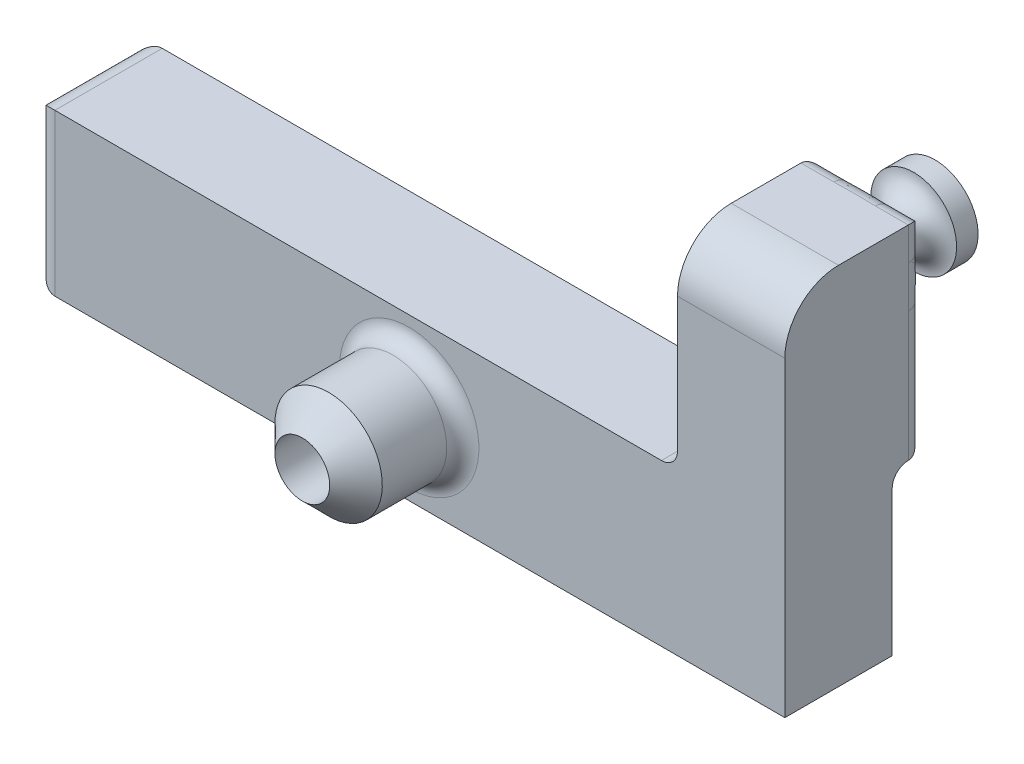
SolidWorks part; units mm, degrees
ref_plane "Front Plane" through (0, 0, 0) normal (0, 0, 1) x (1, 0, 0)
ref_plane "Top Plane" through (0, 0, 0) normal (0, 1, 0) x (1, 0, 0)
ref_plane "Right Plane" through (0, 0, 0) normal (1, 0, 0) x (0, 0, -1)
sketch "Sketch1" plane through (0, 0, 0) normal (0, 0, 1) x (1, 0, 0)
  line L0 (-35, -7.5) -> (35, -7.5)
  line L1 (-35, -7.5) -> (-35, 7.5)
  line L2 (35, -7.5) -> (35, 7.5)
  line L3 (-35, 7.5) -> (35, 7.5)
  line L4 (-35, -7.5) -> (35, 7.5) construction
  line L5 (35, -7.5) -> (-35, 7.5) construction
  circle A0 centre (0, 0) radius 2.55
  point P1 (0, 0)
  dimension "D3" = 5.1
  dimension "D1" = 70
  dimension "D2" = 15
  dimension "D4" = 35
extrude "Boss-Extrude1" add sketch "Sketch1" along normal blind 10
sketch "Sketch5" plane through (0, 0, 0) normal (0, 0, -1) x (-1, 0, 0)
  line L0 (-35, 26.5) -> (-25, 26.5)
  line L1 (-35, 26.5) -> (-35, 7.5)
  line L2 (-25, 26.5) -> (-25, 7.5)
  line L3 (-35, 7.5) -> (-25, 7.5)
  line L7 (-35, 7.5) -> (35, 7.5) construction
  line L8 (-35, -7.5) -> (-35, 7.5) construction
  dimension "D1" = 10
  dimension "D2" = 19
extrude "Boss-Extrude5" add sketch "Sketch5" against normal blind 10 and the other way blind 3 separate body
sketch "Sketch2" plane through (0, 0, 10) normal (0, 0, 1) x (1, 0, 0)
  line L0 (-35, 7.5) -> (-25, 7.5)
  line L1 (-35, 7.5) -> (-35, 17.5)
  line L2 (-25, 7.5) -> (-25, 17.5)
  line L3 (-35, 17.5) -> (-25, 17.5)
  line L4 (35, 7.5) -> (-35, 7.5) construction
  dimension "D1" = 10
  dimension "D2" = 10
extrude "Boss-Extrude2" [suppressed] add sketch "Sketch2" against normal blind 10
sketch "Sketch3" plane through (-35, 0, -3) normal (0, 0, -1) x (-1, 0, 0)
  line L0 (-70, -7.5) -> (-70, 7.5) construction
  line L1 (-60, 7.5) -> (-60, 26.5) construction
  line L2 (-60, 26.5) -> (-70, 26.5) construction
  circle A0 centre (-65, 21.5) radius 2
  point P9 (-60, 17)
  dimension "D1" = 4
  dimension "D2" = 5
  dimension "D3" = 5
fillet "Fillet1" radius 2 4 edges at (-35, 0, 0) (-35, -7.5, 5) (-35, 0, 10) (-35, 7.5, 5)
extrude "Boss-Extrude6" add sketch "Sketch3" along normal blind 4
sketch "Sketch6" plane through (0, 0, -7) normal (0, 0, -1) x (-1, 0, 0)
  circle A2 centre (-30, 21.5) radius 4
  circle A3 centre (-30, 21.5) radius 4
  dimension "D1" = 2
extrude "Boss-Extrude7" add sketch "Sketch6" along normal blind 2
fillet "Fillet4" radius 5 1 edges at (30, 26.5, 10)
combine bodies "Combine1" operation type add bodies to combine 106 105 107 101
fillet "Fillet7" radius 2 2 edges at (28, 21.5, -7) (28, 21.5, -3)
fillet "Fillet3" radius 1.5 5 edges at (30, 7.5, -3) (30, 7.5, 0) (25, 17, -3) (30, 26.5, -3) (35, 17, -3)
fillet "Fillet9" radius 1.5 2 edges at (25, 6.75, 0) (25, 7.5, 5)
sketch "Sketch8" plane through (0, 0, 0) normal (1, 0, 0) x (0, 0, -1)
  line L0 (-10, 0) -> (-20, 0)
  line L1 (-10, 21.5) -> (-10, -7.5) construction
  line L2 (-20, 0) -> (-20, 2.5)
  line L3 (-20, 2.5) -> (-17.5, 5)
  line L4 (-17.5, 5) -> (-10, 5)
  line L5 (-10, 5) -> (-10, 0)
  dimension "D1" = 2.5
  dimension "D2" = 5
  dimension "D3" = 10
  dimension "D4" = 135
revolve "Revolve1" add sketch "Sketch8" angle 360 about L0
sketch "Sketch9" plane through (0, 0, 10) normal (0, 0, -1) x (-1, 0, 0)
  circle A1 centre (0, 0) radius 2.55
  circle A2 centre (0, 0) radius 2.55
  dimension "D1" = 0
extrude "Cut-Extrude1" cut sketch "Sketch9" against normal blind 10
fillet "Fillet10" radius 1.5 1 edges at (0, 5, 10)
sketch "Sketch10" plane through (0, 0, 0) normal (0, 0, -1) x (-1, 0, 0)
  line L1 (33, -7.5) -> (-35, -7.5) construction
  line L2 (-35, -7.5) -> (-35, 6) construction
  line L3 (-35, -5.5) -> (-35, -7.5)
  line L4 (-35, -7.5) -> (-15, -7.5)
  arc A0 (-15, -7.5) -> (-35, -5.5) centre (-15, 93.5) cw
  dimension "D2" = 2
  dimension "D1" = 20
extrude "Cut-Extrude2" [suppressed] cut sketch "Sketch10" against normal blind 10
